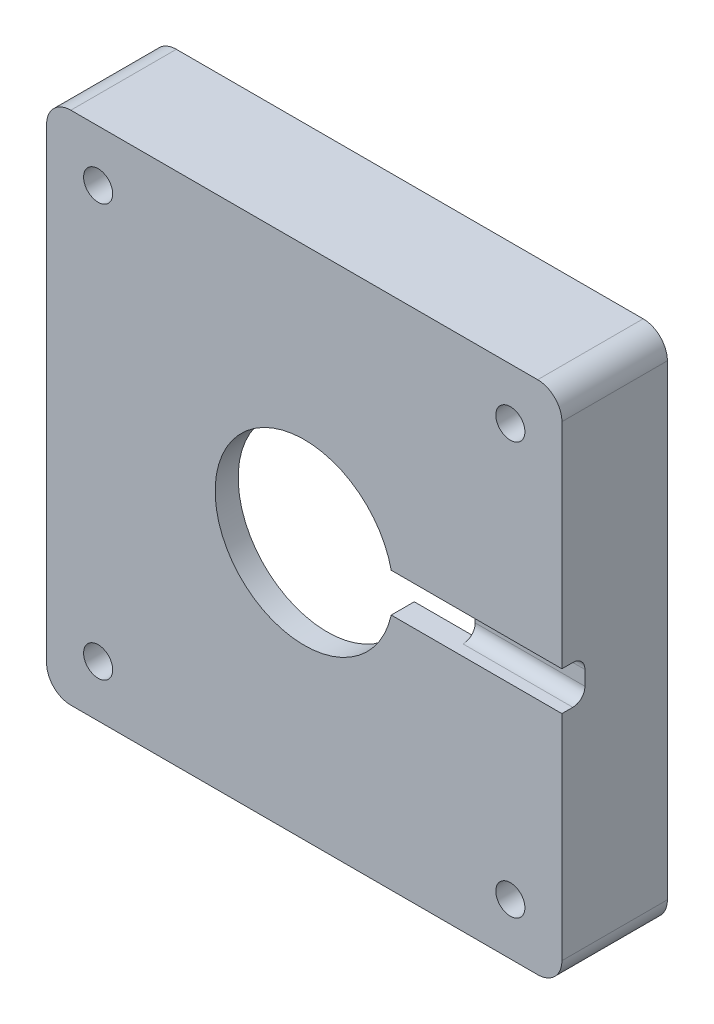
SolidWorks part; units mm, degrees
ref_plane "Front Plane" through (0, 0, 0) normal (0, 0, 1) x (1, 0, 0)
ref_plane "Top Plane" through (0, 0, 0) normal (0, 1, 0) x (1, 0, 0)
ref_plane "Right Plane" through (0, 0, 0) normal (1, 0, 0) x (0, 0, -1)
sketch "Sketch1" plane through (0, 0, 0) normal (0, 0, 1) x (1, 0, 0)
  line L0 (21.25, -19.25) -> (21.25, 19.25) construction
  line L1 (-19.25, -21.25) -> (19.25, -21.25) construction
  line L2 (-21.25, 19.25) -> (-21.25, -19.25) construction
  line L3 (19.25, 21.25) -> (-19.25, 21.25) construction
  line L4 (21.25, -19.25) -> (21.25, 19.25)
  line L5 (-19.25, -21.25) -> (19.25, -21.25)
  line L6 (-21.25, 19.25) -> (-21.25, -19.25)
  line L7 (19.25, 21.25) -> (-19.25, 21.25)
  arc A0 (21.25, 19.25) -> (19.25, 21.25) centre (19.25, 19.25) ccw construction
  arc A1 (19.25, -21.25) -> (21.25, -19.25) centre (19.25, -19.25) ccw construction
  arc A2 (-21.25, -19.25) -> (-19.25, -21.25) centre (-19.25, -19.25) ccw construction
  arc A3 (-19.25, 21.25) -> (-21.25, 19.25) centre (-19.25, 19.25) ccw construction
  arc A4 (21.25, 19.25) -> (19.25, 21.25) centre (19.25, 19.25) ccw
  arc A5 (19.25, -21.25) -> (21.25, -19.25) centre (19.25, -19.25) ccw
  arc A6 (-21.25, -19.25) -> (-19.25, -21.25) centre (-19.25, -19.25) ccw
  arc A7 (-19.25, 21.25) -> (-21.25, 19.25) centre (-19.25, 19.25) ccw
  circle A8 centre (-17, -17) radius 1.2 construction
  circle A9 centre (17, -17) radius 1.2 construction
  circle A10 centre (17, 17) radius 1.2 construction
  circle A11 centre (-17, 17) radius 1.2 construction
  circle A12 centre (-17, -17) radius 1.2
  circle A13 centre (17, -17) radius 1.2
  circle A14 centre (17, 17) radius 1.2
  circle A15 centre (-17, 17) radius 1.2
extrude "Boss-Extrude1" add sketch "Sketch1" along normal offset from surface (8.7 mm away) 2 offset beyond the face yes
sketch "Sketch2" plane through (0, 0, 0) normal (0, 0, -1) x (-1, 0, 0)
  line L0 (19.25, -19.25) -> (-19.25, -19.25) construction
  line L2 (-19.25, 19.25) -> (19.25, 19.25) construction
  line L3 (19.25, 19.25) -> (19.25, -19.25) construction
  line L4 (17, 14.55) -> (19.25, 14.55) construction
  line L5 (14.55, 19.25) -> (14.55, 17) construction
  line L6 (-14.55, 17) -> (-14.55, 19.25) construction
  line L7 (-19.25, 14.55) -> (-17, 14.55) construction
  line L8 (-14.55, -19.25) -> (-14.55, -17) construction
  line L9 (-17, -14.55) -> (-19.25, -14.55) construction
  line L10 (19.25, -14.55) -> (17, -14.55) construction
  line L11 (14.55, -17) -> (14.55, -19.25) construction
  line L12 (14.55, -19.25) -> (-14.55, -19.25)
  line L13 (-19.25, -14.55) -> (-19.25, 14.55)
  line L14 (-14.55, 19.25) -> (14.55, 19.25)
  line L15 (19.25, 14.55) -> (19.25, -14.55)
  line L16 (17, 14.55) -> (19.25, 14.55)
  line L17 (14.55, 19.25) -> (14.55, 17)
  line L18 (-14.55, 17) -> (-14.55, 19.25)
  line L19 (-19.25, 14.55) -> (-17, 14.55)
  line L20 (-14.55, -19.25) -> (-14.55, -17)
  line L21 (-17, -14.55) -> (-19.25, -14.55)
  line L22 (19.25, -14.55) -> (17, -14.55)
  line L23 (14.55, -17) -> (14.55, -19.25)
  arc A0 (14.55, 17) -> (17, 14.55) centre (17, 17) ccw construction
  arc A1 (-17, 14.55) -> (-14.55, 17) centre (-17, 17) ccw construction
  arc A2 (-14.55, -17) -> (-17, -14.55) centre (-17, -17) ccw construction
  arc A3 (17, -14.55) -> (14.55, -17) centre (17, -17) ccw construction
  arc A4 (14.55, 17) -> (17, 14.55) centre (17, 17) ccw
  arc A5 (-17, 14.55) -> (-14.55, 17) centre (-17, 17) ccw
  arc A6 (-14.55, -17) -> (-17, -14.55) centre (-17, -17) ccw
  arc A7 (17, -14.55) -> (14.55, -17) centre (17, -17) ccw
extrude "Cut-Extrude2" cut sketch "Sketch2" against normal blind 3
sketch "Sketch3" plane through (0, 0, 3) normal (0, 0, -1) x (-1, 0, 0)
  line L0 (-12, -6) -> (-12, 6) construction
  line L1 (5, -13) -> (-5, -13) construction
  line L2 (12, 6) -> (12, -6) construction
  line L3 (-5, 13) -> (5, 13) construction
  line L4 (-12, -6) -> (-12, 6) construction
  line L5 (5, -13) -> (-5, -13) construction
  line L6 (12, 6) -> (12, -6) construction
  line L7 (-5, 13) -> (5, 13) construction
  line L8 (-12.2, -6) -> (-12.2, 6)
  line L9 (-5, 13.2) -> (5, 13.2)
  line L10 (12.2, 6) -> (12.2, -6)
  line L11 (5, -13.2) -> (-5, -13.2)
  arc A0 (-5, 13) -> (-12, 6) centre (-5, 6) ccw construction
  arc A1 (-12, -6) -> (-5, -13) centre (-5, -6) ccw construction
  arc A2 (5, -13) -> (12, -6) centre (5, -6) ccw construction
  arc A3 (12, 6) -> (5, 13) centre (5, 6) ccw construction
  arc A4 (-5, 13) -> (-12, 6) centre (-5, 6) ccw construction
  arc A5 (-12, -6) -> (-5, -13) centre (-5, -6) ccw construction
  arc A6 (5, -13) -> (12, -6) centre (5, -6) ccw construction
  arc A7 (12, 6) -> (5, 13) centre (5, 6) ccw construction
  arc A8 (-5, 13.2) -> (-12.2, 6) centre (-5, 6) ccw
  arc A9 (12.2, 6) -> (5, 13.2) centre (5, 6) ccw
  arc A10 (5, -13.2) -> (12.2, -6) centre (5, -6) ccw
  arc A11 (-12.2, -6) -> (-5, -13.2) centre (-5, -6) ccw
  dimension "D1" = 0.2
extrude "Cut-Extrude3" cut sketch "Sketch3" against normal blind 3.8
sketch "Sketch4" plane through (0, 0, 8.7) normal (0, 0, 1) x (1, 0, 0)
  line L3 (7.0308, -1.3) -> (7.95, -1.3)
  line L4 (7.95, -1.3) -> (7.95, 1.3)
  line L5 (7.95, 1.3) -> (7.0308, 1.3)
  line L9 (7.95, -1.3) -> (7.95, 1.3) construction
  line L10 (8.15, -1.5) -> (8.15, 1.5) construction
  line L11 (8.15, 1.5) -> (7.1953, 1.5) construction
  line L12 (7.95, 1.3) -> (7.0308, 1.3) construction
  line L13 (7.0308, -1.3) -> (7.95, -1.3) construction
  line L14 (7.1953, -1.5) -> (8.15, -1.5) construction
  line L15 (21.25, 19.25) -> (21.25, -19.25) construction
  line L16 (21.25, 1.6) -> (7.1737, 1.6)
  line L17 (21.25, 1.6) -> (21.25, -1.6)
  line L18 (21.25, -1.6) -> (7.1737, -1.6)
  line L21 (21.25, 0) -> (0, 0) construction
  arc A0 (7.1737, 1.6) -> (7.1737, -1.6) centre (0, 0) ccw
  arc A1 (7.0308, 1.3) -> (7.0308, -1.3) centre (0, 0) ccw
  arc A2 (7.0308, 1.3) -> (7.0308, -1.3) centre (0, 0) ccw construction
  arc A3 (7.1953, 1.5) -> (7.1953, -1.5) centre (0, 0) ccw construction
  dimension "D3" = 3.2
  dimension "D1" = 0
  dimension "D2" = 0.2
extrude "Cut-Extrude4" cut sketch "Sketch4" against normal up to surface (1.9 mm away) up to face at (0, 0, 6.8)
sketch "Sketch5" plane through (0, 0, 0) normal (0, 0, -1) x (-1, 0, 0)
  line L0 (-19.25, 14.55) -> (-19.25, -14.55) construction
  line L1 (-19.25, -11.05) -> (-20.25, -11.05)
  line L2 (-19.25, -11.05) -> (-19.25, -9.55)
  line L3 (-19.25, -9.55) -> (-20.25, -9.55)
  line L4 (-20.25, -11.05) -> (-20.25, -9.55)
  line L5 (-19.75, -9.55) -> (-19.75, -11.05) construction
  line L6 (-19.25, -10.3) -> (-20.25, -10.3) construction
  point P356 (-19.75, -10.3)
  dimension "D1" = 8
  dimension "D2" = 1.5
  dimension "D3" = 1
extrude "Cut-Extrude5" cut sketch "Sketch5" against normal up to surface (3 mm away) up to face at (0, 0, 3)
fillet "Fillet1" radius 1 4 edges at (19.25, -11.05, 1.5) (19.25, -9.55, 1.5) (16.725, -1.6, 6.8) (16.725, 1.6, 6.8)
